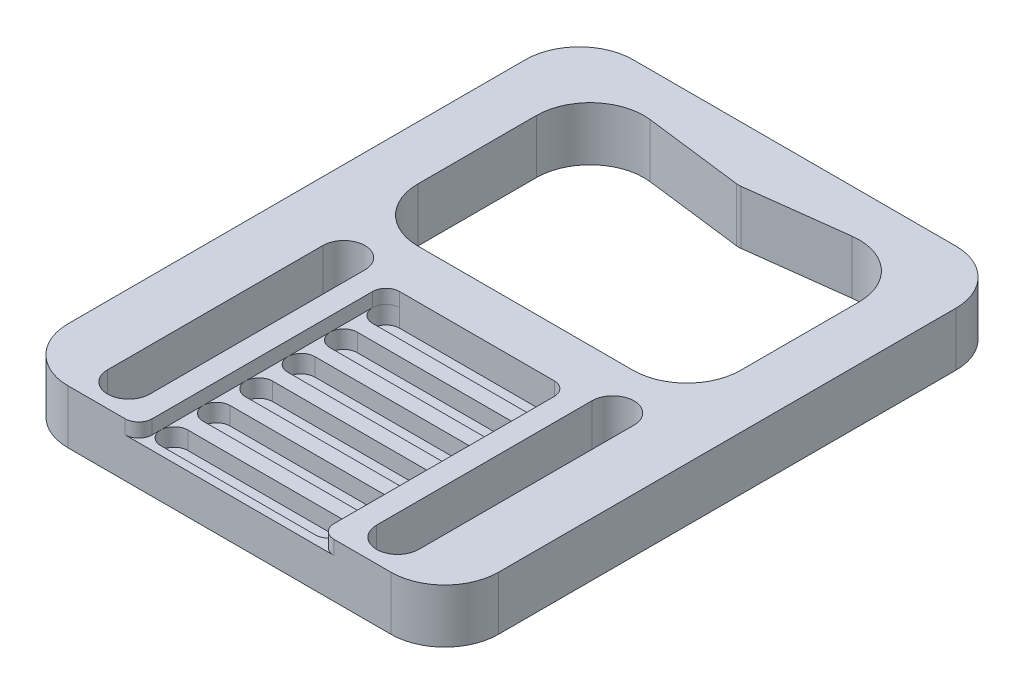
SolidWorks part; units mm, degrees
material "6061-T6 (SS)"
ref_plane "Front Plane" through (0, 0, 0) normal (0, 0, 1) x (1, 0, 0)
ref_plane "Top Plane" through (0, 0, 0) normal (0, 1, 0) x (1, 0, 0)
ref_plane "Right Plane" through (0, 0, 0) normal (1, 0, 0) x (0, 0, -1)
sketch "Sketch1" plane through (0, 0, 0) normal (0, 1, 0) x (1, 0, 0)
  line L0 (25.4, 34.925) -> (25.4, 0) construction
  line L1 (0, 0) -> (50.8, 0)
  line L2 (0, 0) -> (0, 66.675)
  line L3 (0, 66.675) -> (50.8, 66.675)
  line L4 (50.8, 0) -> (50.8, 66.675)
  line L6 (6.35, 62.4522) -> (6.35, 34.925)
  line L7 (6.35, 34.925) -> (44.45, 34.925)
  line L8 (44.45, 62.4522) -> (44.45, 34.925)
  line L11 (6.35, 62.4522) -> (25.4, 60.071)
  line L12 (25.4, 60.071) -> (44.45, 62.4522)
  line L13 (9.525, 29.3687) -> (9.525, 3.9687) construction
  line L14 (12.0142, 29.3687) -> (12.0142, 3.9688)
  line L15 (7.0358, 29.3687) -> (7.0358, 3.9688)
  line L16 (41.275, 29.3688) -> (41.275, 3.9688) construction
  line L17 (43.7642, 29.3687) -> (43.7642, 3.9688)
  line L18 (38.7858, 29.3687) -> (38.7858, 3.9688)
  line L19 (9.525, 16.6687) -> (41.275, 16.6687) construction
  circle A0 centre (25.4, 53.213) radius 6.858 construction
  circle A1 centre (25.4, 53.213) radius 15.748 construction
  arc A6 (12.0142, 29.3687) -> (7.0358, 29.3687) centre (9.525, 29.3687) ccw
  arc A7 (7.0358, 3.9688) -> (12.0142, 3.9688) centre (9.525, 3.9687) ccw
  arc A8 (43.7642, 29.3687) -> (38.7858, 29.3687) centre (41.275, 29.3688) ccw
  arc A9 (38.7858, 3.9688) -> (43.7642, 3.9688) centre (41.275, 3.9688) ccw
  arc A10 (25.1519, 60.102) -> (25.6481, 60.102) centre (25.4, 62.0866) ccw
  point P18 (9.525, 16.6687)
  point P23 (41.275, 16.6688)
  point P30 (25.4, 16.6687)
  point P33 (25.4, 55.4355)
  point P37 (0, 0)
  point P38 (0, 0)
  point P39 (0, 0)
  point P42 (26.2502, 39.7105)
  dimension "D4" = 31.496
  dimension "D5" = 13.716
  dimension "D8" = 2.4892
  dimension "D12" = 2
  dimension "D1" = 50.8
  dimension "D2" = 66.675
  dimension "D6" = 38.1
  dimension "D7" = 2.3813
  dimension "D9" = 3.9688
  dimension "D10" = 25.4
  dimension "D11" = 31.75
  dimension "D14" = 34.925
  dimension "D13" = 2.54
extrude "Boss-Extrude1" add sketch "Sketch1" along normal mid plane 6.35 contours L1 L4 L3 L2 A9 L18 A8 L17 A7 L15 A6 L14 L11 A10 L12 L8 L7 L6 region at (25.4, 0, -28.5805)
fillet "Fillet1" radius 6.35 8 edges at (6.35, 0, -62.4522) (6.35, 0, -34.925) (44.45, 0, -34.925) (44.45, 0, -62.4522) (0, 0, -66.675) (50.8, 0, -66.675) (0, 0, 0) (50.8, 0, 0)
sketch "Sketch3" plane through (0, 3.175, 0) normal (0, 1, 0) x (1, 0, 0)
  line L1 (14.675, 0) -> (36.125, 0)
  line L2 (14.675, 0) -> (14.675, 29.2)
  line L3 (14.675, 29.2) -> (36.125, 29.2)
  line L4 (36.125, 0) -> (36.125, 29.2)
  line L5 (25.4, 29.2) -> (25.4, 34.925) construction
  line L7 (6.35, 0) -> (44.45, 0) construction
  line L8 (12.7, 34.925) -> (38.1, 34.925) construction
  point P4 (14.675, 0)
  point P8 (0, 0)
  point P9 (25.4, 38.1)
  point P10 (0, 0)
  dimension "D1" = 21.45
  dimension "D2" = 29.2
extrude "Cut-Extrude2" cut sketch "Sketch3" against normal blind 1.65
sketch "Sketch2" plane through (0, 1.525, 0) normal (0, 1, 0) x (1, 0, 0)
  line L0 (16.275, 4.2) -> (34.525, 4.2)
  line L1 (16.275, 1) -> (34.525, 1)
  line L2 (25.4, 1) -> (25.4, 0) construction
  line L3 (16.275, 29.2) -> (34.525, 29.2)
  line L4 (16.275, 9.2) -> (34.525, 9.2)
  line L5 (16.275, 6) -> (34.525, 6)
  line L6 (16.275, 14.2) -> (34.525, 14.2)
  line L7 (16.275, 11) -> (34.525, 11)
  line L8 (16.275, 19.2) -> (34.525, 19.2)
  line L9 (16.275, 16) -> (34.525, 16)
  line L10 (16.275, 24.2) -> (34.525, 24.2)
  line L11 (16.275, 21) -> (34.525, 21)
  line L16 (16.275, 26) -> (34.525, 26)
  line L17 (14.675, 0) -> (36.125, 0) construction
  arc A0 (16.275, 1) -> (16.275, 4.2) centre (16.275, 2.6) cw
  arc A1 (34.525, 4.2) -> (34.525, 1) centre (34.525, 2.6) cw
  arc A2 (16.275, 6) -> (16.275, 9.2) centre (16.275, 7.6) cw
  arc A3 (34.525, 9.2) -> (34.525, 6) centre (34.525, 7.6) cw
  arc A4 (16.275, 11) -> (16.275, 14.2) centre (16.275, 12.6) cw
  arc A5 (34.525, 14.2) -> (34.525, 11) centre (34.525, 12.6) cw
  arc A6 (16.275, 16) -> (16.275, 19.2) centre (16.275, 17.6) cw
  arc A7 (34.525, 19.2) -> (34.525, 16) centre (34.525, 17.6) cw
  arc A8 (16.275, 21) -> (16.275, 24.2) centre (16.275, 22.6) cw
  arc A9 (34.525, 24.2) -> (34.525, 21) centre (34.525, 22.6) cw
  arc A10 (16.275, 26) -> (16.275, 29.2) centre (16.275, 27.6) cw
  arc A11 (34.525, 29.2) -> (34.525, 26) centre (34.525, 27.6) cw
  point P8 (26.2796, 0)
  dimension "D1" = 3.2
  dimension "D2" = 18.25
  dimension "D5" = 5
  dimension "D3" = 1
  dimension "D4" = 6
extrude "Cut-Extrude1" cut sketch "Sketch2" against normal blind 2.1
fillet "Fillet2" radius 1.6 4 edges at (36.125, 2.35, 0) (36.125, 2.35, -29.2) (14.675, 2.35, -29.2) (14.675, 2.35, 0)
equation "\"D5@Sketch2\"=5mm"
equation "\"D1@Sketch2\"=3.2mm"
equation "\"D2@Sketch2\"=18.25mm"
equation "\"D1@Sketch3\"=18.25mm+3.2mm"
equation "\"D1@Cut-Extrude2\"=(3.73mm - 2.08mm)"
equation "\"D2@Sketch3\"=29.2mm"
equation "\"D1@Cut-Extrude1\"=2.1mm"
equation "\"D1@Fillet2\"=1.6mm"
equation "\"D12@Sketch1\"=2mm"
equation "\"D3@Sketch2\"=1mm"
